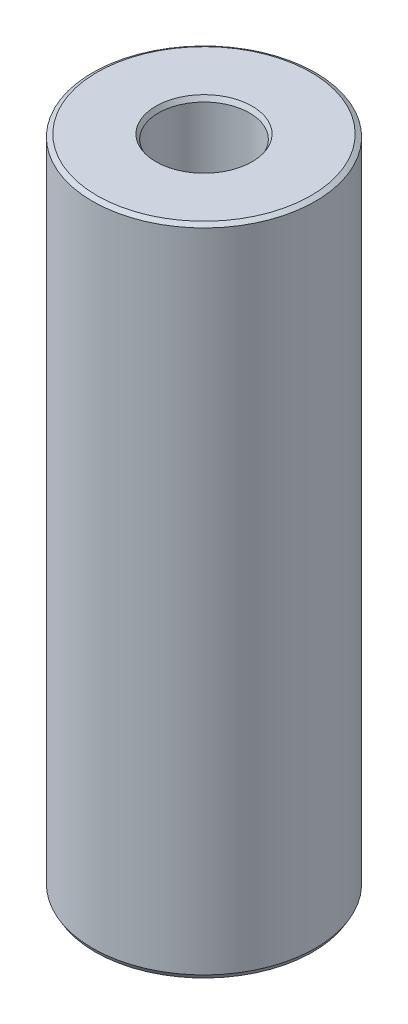
SolidWorks part; units mm, degrees
ref_plane "Front Plane" through (0, 0, 0) normal (0, 0, 1) x (1, 0, 0)
ref_plane "Top Plane" through (0, 0, 0) normal (0, 1, 0) x (1, 0, 0)
ref_plane "Right Plane" through (0, 0, 0) normal (1, 0, 0) x (0, 0, -1)
sketch "Sketch1" plane through (0, 0, 0) normal (0, 1, 0) x (1, 0, 0)
  circle A0 centre (0, 0) radius 47.5
  dimension "SLEEVE_OD" = 95
extrude "Boss-Extrude1" add sketch "Sketch1" along normal blind 278.7389
sketch "Sketch2" plane through (0, 0, 0) normal (0, 1, 0) x (1, 0, 0)
  circle A0 centre (0, 0) radius 19.4095
  dimension "BORE_D" = 38.8189
extrude "Cut-Extrude1" cut sketch "Sketch2" along normal through all
chamfer "Chamfer1" distance 1.1162 angle 60 4 edges at (0, 278.7389, 19.4095) (0, 0, 19.4095) (0, 0, 47.5) (0, 278.7389, 47.5) first distance on face at (0, 278.7389, 19.4095) first distance on face at (0, 0, 19.4095) first distance on face at (0, 278.7389, 47.5)
